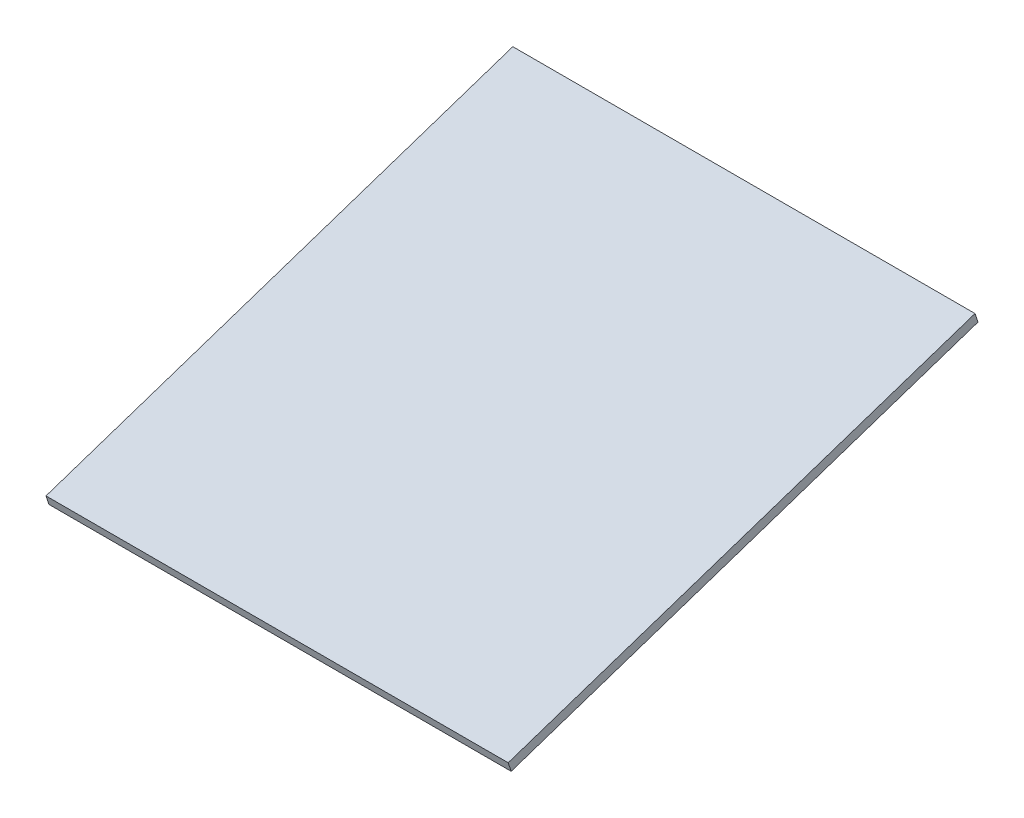
SolidWorks part; units mm, degrees
ref_plane "Alzado" through (0, 0, 0) normal (0, 0, 1) x (1, 0, 0)
ref_plane "Planta" through (0, 0, 0) normal (0, 1, 0) x (1, 0, 0)
ref_plane "Vista lateral" through (0, 0, 0) normal (1, 0, 0) x (0, 0, -1)
sketch "Croquis1" plane through (0, 0, 0) normal (1, 0, 0) x (0, 0, -1)
  line L0 (-70.2512, -24.9171) -> (71.1512, 22.2171)
  line L1 (-71.1512, -22.2171) -> (-70.2512, -24.9171)
  line L2 (57.8488, 9.7829) -> (-40.1512, -22.8837) construction
  line L3 (57.3488, 9.6163) -> (-39.6512, -22.7171)
  line L4 (70.2512, 24.9171) -> (71.1512, 22.2171)
  line L6 (-71.1512, -22.2171) -> (70.2512, 24.9171)
  line L9 (-39.6512, -22.19) -> (-39.6512, -15.2441) construction
  line L10 (57.3488, 17.6163) -> (57.3488, 9.6163)
  line L11 (57.3488, 17.0892) -> (57.3488, 10.1433) construction
  line L12 (-39.6512, -22.7171) -> (-39.6512, -14.7171)
  line L13 (-39.6512, -15.2441) -> (57.3488, 17.0892) construction
  line L14 (57.3488, 10.1433) -> (-39.6512, -22.19) construction
  line L15 (57.8488, 17.7829) -> (57.8488, 9.7829) construction
  line L17 (-40.1512, -14.8837) -> (57.8488, 17.7829) construction
  line L20 (-40.1512, -22.8837) -> (-40.1512, -14.8837) construction
  dimension "D2" = 71.565
  dimension "D7" = 8
  dimension "D9" = 14.5491
  dimension "D10" = 8
  dimension "D11" = 102.247
  dimension "D5" = 108.435
extrude "Saliente-Extruir1" add sketch "Croquis1" along normal blind 140 contours L6 region at (0, 0, 0)
extrude "Saliente-Extruir2" add sketch "Croquis1<3>" along normal blind 8 from offset 13.3 contours L12 L3 L10 region at (0, -2.5504, -8.8488)
sketch "Croquis1<3>" plane through (0, 0, 0) normal (1, 0, 0) x (0, 0, -1) same geometry as "Croquis1"
extrude "Saliente-Extruir3" add sketch "Croquis1<4>" along normal blind 8 from offset 119 contours L12 L3 L10 region at (0, -2.5504, -8.8488)
sketch "Croquis1<4>" plane through (0, 0, 0) normal (1, 0, 0) x (0, 0, -1) same geometry as "Croquis1"
